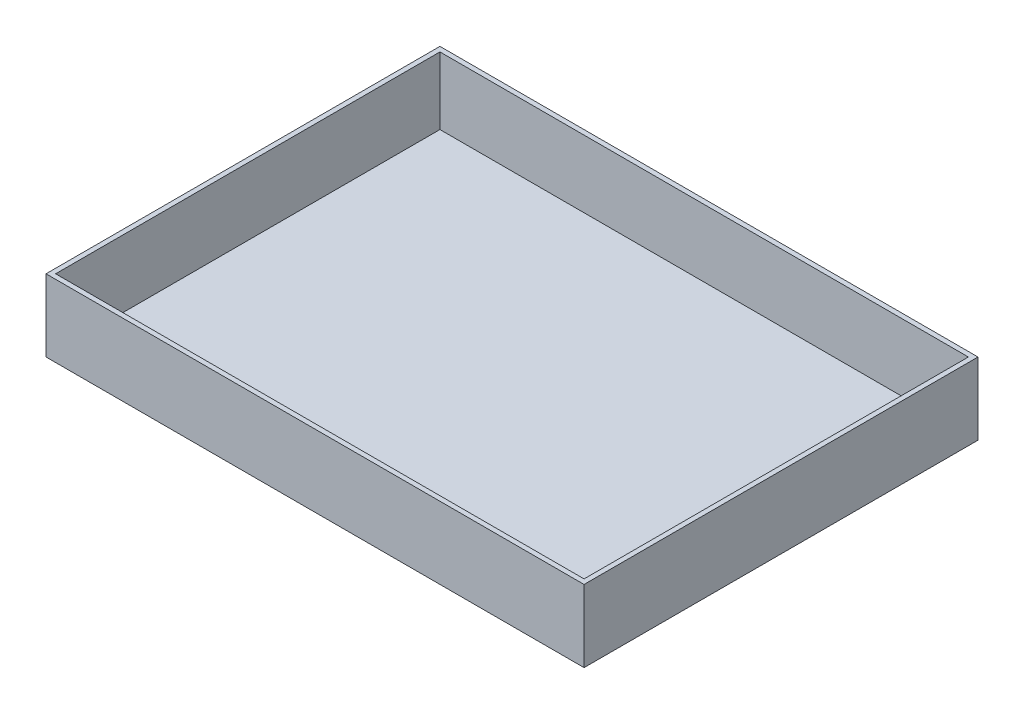
SolidWorks part; units mm, degrees
ref_plane "正面" through (0, 0, 0) normal (0, 0, 1) x (1, 0, 0)
ref_plane "平面" through (0, 0, 0) normal (0, 1, 0) x (1, 0, 0)
ref_plane "右側面" through (0, 0, 0) normal (1, 0, 0) x (0, 0, -1)
sketch "ｽｹｯﾁ1" plane through (0, 0, 0) normal (0, 1, 0) x (1, 0, 0)
  line L1 (-280, 205) -> (280, 205)
  line L2 (-280, 205) -> (-280, -205)
  line L3 (-280, -205) -> (280, -205)
  line L4 (280, 205) -> (280, -205)
  line L5 (-280, 205) -> (280, -205) construction
  line L6 (-280, -205) -> (280, 205) construction
  point P0 (0, 0)
  dimension "D1" = 410
  dimension "600" = 560
extrude "ﾎﾞｽ - 押し出し1" add sketch "ｽｹｯﾁ1" along normal blind 75
shell "ｼｪﾙ1" thickness 5 removed face at (0, 75, 0)
